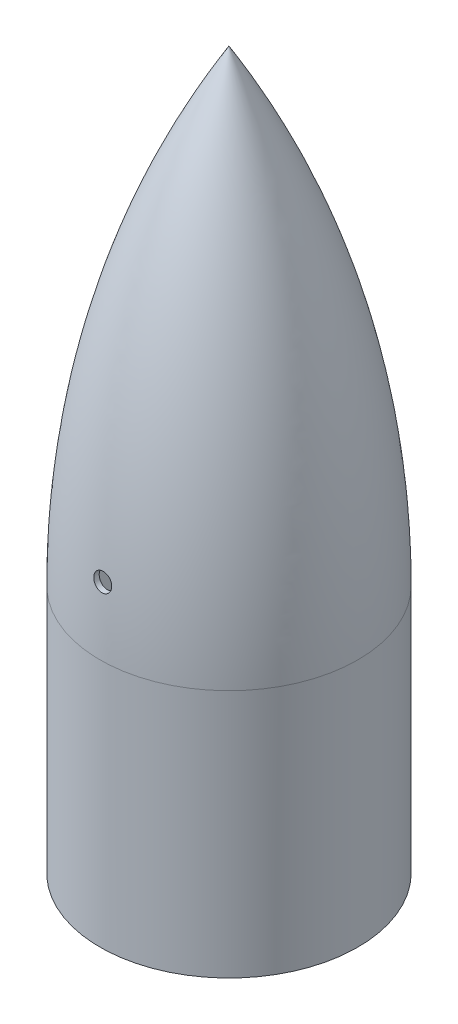
SolidWorks part; units mm, degrees
ref_plane "Front Plane" through (0, 0, 0) normal (0, 0, 1) x (1, 0, 0)
ref_plane "Top Plane" through (0, 0, 0) normal (0, 1, 0) x (1, 0, 0)
ref_plane "Right Plane" through (0, 0, 0) normal (1, 0, 0) x (0, 0, -1)
sketch "Sketch1" plane through (0, 0, 0) normal (0, 0, 1) x (1, 0, 0)
  line L0 (0, 0) -> (18.288, 0)
  line L1 (0, 0) -> (0, 101.6)
  line L5 (18.288, 0) -> (18.288, 35.306)
  spline S0 degree 2 poles (0, 101.6) (18.2037, 70.9775) (18.288, 35.306) knots 0 0 0 1 1 1
  dimension "D1" = 101.6
  dimension "D2" = 18.288
  dimension "D3" = 35.306
revolve "Revolve1" add sketch "Sketch1" angle 360 about L1
shell "Shell1" thickness 0.762 removed face at (0, 0, -18.288)
sketch "Sketch2" plane through (0, 0, 0) normal (0, 0, 1) x (1, 0, 0)
  line L0 (18.288, 35.306) -> (-18.288, 35.306) construction
  circle A0 centre (0, 44.704) radius 1.27
  dimension "D1" = 2.54
  dimension "D2" = 9.398
extrude "Cut-Extrude1" cut sketch "Sketch2" against normal through all both and the other way through all
